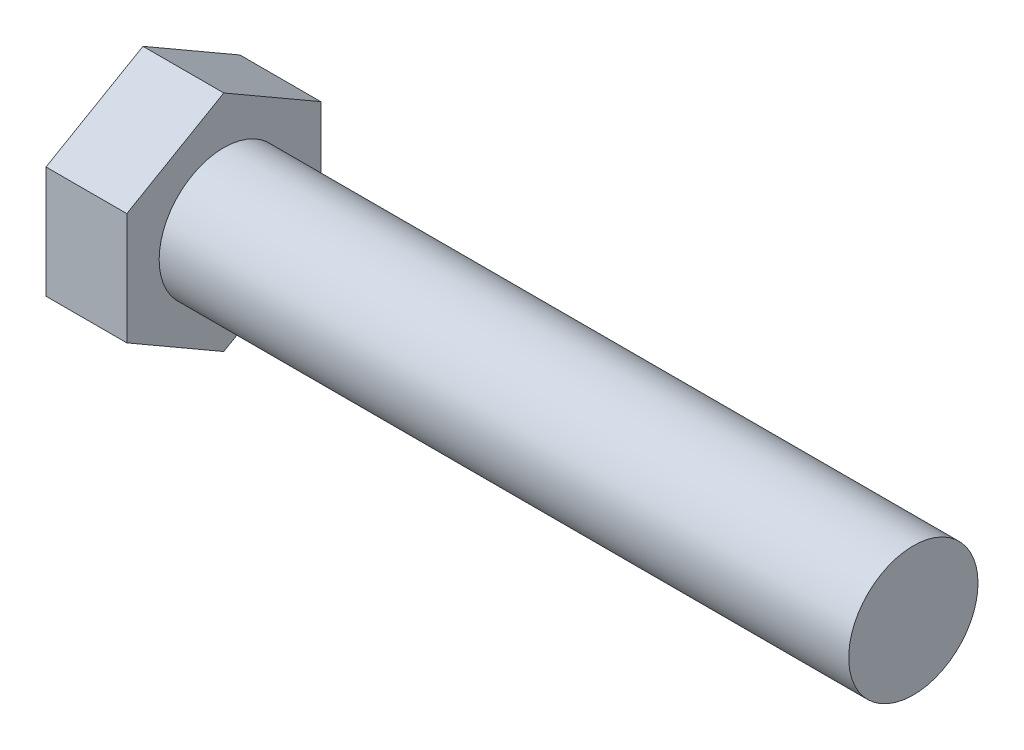
SolidWorks part; units mm, degrees
ref_plane "Front Plane" through (0, 0, 0) normal (0, 0, 1) x (1, 0, 0)
ref_plane "Top Plane" through (0, 0, 0) normal (0, 1, 0) x (1, 0, 0)
ref_plane "Right Plane" through (0, 0, 0) normal (1, 0, 0) x (0, 0, -1)
sketch "Sketch1" plane through (0, 0, 0) normal (0, 0, 1) x (1, 0, 0)
  line L0 (-28.3766, 0) -> (28.3766, 0) construction
  line L1 (28.3766, 4.7625) -> (28.3766, -4.7625) construction
  line L2 (-22.4234, 7.1437) -> (-22.4234, -7.1437) construction
  line L3 (-28.3766, 7.1437) -> (-28.3766, -7.1437) construction
  point P9 (-22.4234, 0)
  point P10 (24.6724, -4.7625)
  point P11 (2.9766, 0)
  dimension "Screw Dia" = 9.525
  dimension "Hex" = 14.2875
  dimension "Head Ht" = 5.9531
  dimension "Screw Length" = 50.8
  dimension "D1" = 3.7042
  dimension "Thread Length" = 25.4
ref_plane "Plane2" through (28.3766, 0, 0) normal (1, 0, 0) x (0, 0, -1)
sketch "Sketch5" plane through (28.3766, 0, 0) normal (1, 0, 0) x (0, 0, -1)
  circle A0 centre (0, 0) radius 4.7625
extrude "Boss-Extrude3" add sketch "Sketch5" against normal up to vertex (50.8 mm away) up to point (-22.4234, 0, 0)
sketch "Sketch9" [suppressed] plane through (28.3766, 0, 0) normal (1, 0, 0) x (0, 0, -1)
  circle A1 centre (0, 0) radius 4.7625
  circle A2 centre (0, 0) radius 4.7625
  dimension "D1" = 0
chamfer "Chamfer1" [suppressed] distance 0.7938 angle 45
sketch "Sketch11" plane through (0, 0, 0) normal (0, 0, 1) x (1, 0, 0)
  line L0 (-22.4234, 4.7625) -> (-22.4234, 0)
  line L1 (-22.4234, 0) -> (14.0891, 0)
  line L3 (14.0891, 0) -> (9.3266, 4.7625)
  line L4 (-22.4234, 4.7625) -> (9.3266, 4.7625)
  dimension "D1" = 45
  dimension "MIn Thread" = 19.05
revolve "Revolve1" add sketch "Sketch11" angle 360 about L1
sketch "Sketch6" plane through (-22.4234, 0, 0) normal (-1, 0, 0) x (0, 0, 1)
  line L0 (0, 7.1437) -> (0, -7.1437) construction
  line L1 (7.1437, 4.1244) -> (0, 8.2489)
  line L2 (0, 8.2489) -> (-7.1438, 4.1244)
  line L3 (-7.1438, 4.1244) -> (-7.1438, -4.1244)
  line L4 (-7.1438, -4.1244) -> (0, -8.2489)
  line L5 (0, -8.2489) -> (7.1437, -4.1244)
  line L6 (7.1437, -4.1244) -> (7.1437, 4.1244)
  circle A0 centre (0, 0) radius 7.1438 construction
extrude "Boss-Extrude4" add sketch "Sketch6" along normal up to vertex (5.9531 mm away) up to point (-28.3766, -7.1437, 0)
sketch "Sketch7" plane through (-28.3766, 0, 0) normal (-1, 0, 0) x (0, 0, 1)
  circle A0 centre (0, 0) radius 7.1438 construction
  circle A1 centre (0, 0) radius 7.1438
sketch "Sketch8" plane through (-28.3766, 0, 0) normal (-1, 0, 0) x (0, 0, 1)
  circle A0 centre (0, 0) radius 7.1438 construction
  circle A1 centre (0, 0) radius 7.1438
extrude "Cut-Extrude3" [suppressed] cut sketch "Sketch8" against normal through all draft 60 flip side to cut
sketch "Sketch12" plane through (-28.3766, 0, 0) normal (-1, 0, 0) x (0, 0, 1)
  line L0 (0, 5.5007) -> (0, 3.0718) construction
  line L1 (0.2143, 5.5007) -> (0.2143, 3.0718)
  line L2 (-0.2143, 5.5007) -> (-0.2143, 3.0718)
  line L3 (0, 4.7625) -> (0, -4.7625) construction
  arc A0 (0.2143, 5.5007) -> (-0.2143, 5.5007) centre (0, 5.5007) ccw
  arc A1 (-0.2143, 3.0718) -> (0.2143, 3.0718) centre (0, 3.0718) ccw
  circle A3 centre (0, 0) radius 2.8575 construction
  circle A4 centre (0, 0) radius 5.715 construction
  point P2 (0, 4.2862)
  dimension "D1" = 5.715
  dimension "D3" = 11.43
  dimension "D2" = 0.4286
extrude "Cut-Extrude4" [suppressed] cut sketch "Sketch12" against normal blind 0.254
pattern_circular "CirPattern1" [suppressed] count 6 over 360 of bodies 116
ref_plane "Plane3" through (2.9766, 0, 0) normal (1, 0, 0) x (0, 0, -1)
split "Split1" [suppressed] bodies to split 105 117
curve "Helix/Spiral1" [suppressed] pitch 1.0583 height 26.4583 turns 25 parameters "Pitch"=1.0583
sketch "Sketch10" [suppressed] plane through (0, 0, 0) normal (0, 0, 1) x (1, 0, 0)
  line L0 (28.3766, 4.7625) -> (28.7734, 4.0751)
  line L1 (28.7734, 4.0751) -> (28.9057, 4.0751)
  line L2 (28.9057, 4.0751) -> (29.3026, 4.7625)
  line L3 (28.3766, 4.7625) -> (29.3026, 4.7625)
  line L4 (28.8396, 4.7625) -> (28.8396, 4.0751) construction
  line L5 (28.575, 4.4188) -> (29.1042, 4.4188) construction
  dimension "D1" = 60
  dimension "D2" = 0.1323
  dimension "D3" = 0.5292
sweep "Cut-Sweep1" [suppressed] cut profiles "Sketch10" path "Helix/Spiral1"
sketch "Sketch13" [suppressed] plane through (2.9766, 0, 0) normal (1, 0, 0) x (0, 0, -1)
  circle A1 centre (0, 0) radius 4.7625
  circle A2 centre (0, 0) radius 4.7625
  dimension "D1" = 0
extrude "Boss-Extrude5" [suppressed] add sketch "Sketch13" along normal through all draft 60
equation "\"D2@Sketch10\" = \"Pitch@Helix/Spiral1\"*.125"
equation "\"D3@Sketch10\" = \"Pitch@Helix/Spiral1\"*.5"
equation "\"D3@Helix/Spiral1\"=\"Thread Length@Sketch1\"+\"Pitch@Helix/Spiral1\""
equation "\"D1@Chamfer1\" = \"Pitch@Helix/Spiral1\"*.75"
equation "\"D1@Sketch12\" = \"Hex@Sketch1\"*.4"
equation "\"D3@Sketch12\" = \"Hex@Sketch1\"*.8"
equation "\"D2@Sketch12\" = \"Hex@Sketch1\"*.03"
equation "\"D1@Sketch1\" = \"Pitch@Helix/Spiral1\"*3.5"
